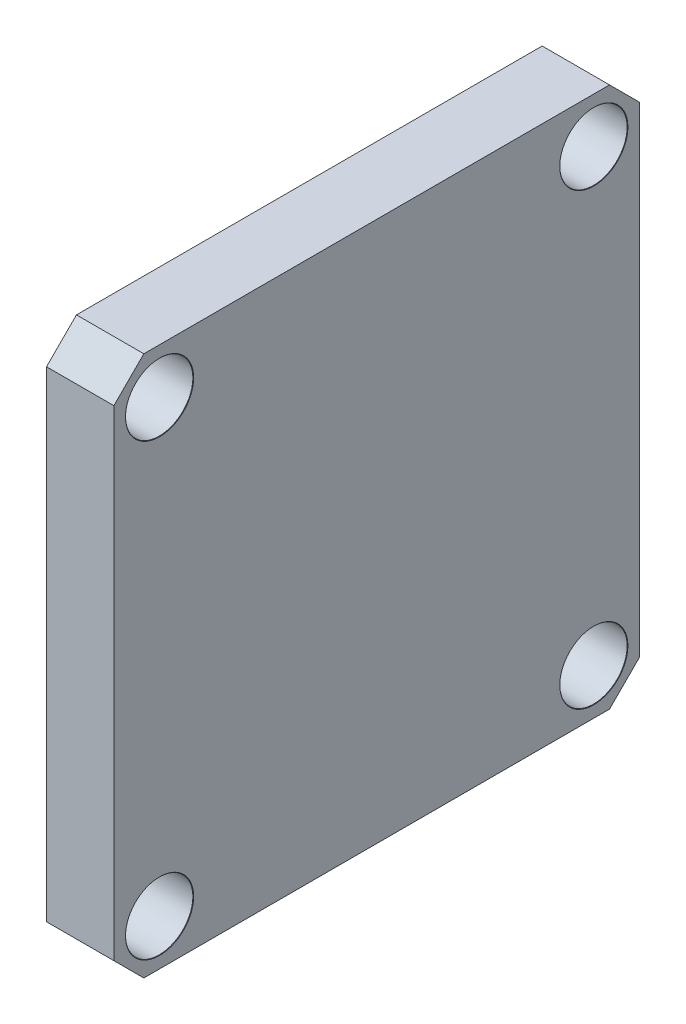
SolidWorks part; units mm, degrees
ref_plane "Спереди" through (0, 0, 0) normal (0, 0, 1) x (1, 0, 0)
ref_plane "Сверху" through (0, 0, 0) normal (0, 1, 0) x (1, 0, 0)
ref_plane "Справа" through (0, 0, 0) normal (1, 0, 0) x (0, 0, -1)
sketch "Эскиз1" plane through (0, 0, 0) normal (1, 0, 0) x (0, 0, -1)
  line L1 (-17.55, -18.05) -> (17.55, -18.05)
  line L2 (-17.55, -18.05) -> (-17.55, 18.05)
  line L3 (-17.55, 18.05) -> (17.55, 18.05)
  line L4 (17.55, -18.05) -> (17.55, 18.05)
  line L5 (-17.55, -18.05) -> (17.55, 18.05) construction
  line L6 (-17.55, 18.05) -> (17.55, -18.05) construction
  point P0 (0, 0)
  dimension "D1" = 36.1
  dimension "D2" = 35.1
extrude "Бобышка-Вытянуть1" add sketch "Эскиз1" along normal blind 4.5
chamfer "Фаска1" distance 2 angle 45 4 edges at (2.25, -18.05, -17.55) (2.25, 18.05, -17.55) (2.25, -18.05, 17.55) (2.25, 18.05, 17.55)
ref_axis "Ось1" through (-17.3885, 0, 0) along (1, 0, 0)
sketch "Эскиз2" plane through (4.5, 0, 0) normal (1, 0, 0) x (0, 0, -1)
  line L1 (-14.5, -15) -> (14.5, -15)
  line L2 (-14.5, -15) -> (-14.5, 15)
  line L3 (-14.5, 15) -> (14.5, 15)
  line L4 (14.5, -15) -> (14.5, 15)
  line L5 (-14.5, -15) -> (14.5, 15) construction
  line L6 (-14.5, 15) -> (14.5, -15) construction
  point P0 (0, 0)
  dimension "D1" = 29
  dimension "D2" = 30
hole_wizard "Отверстие с зазором M41" positions "Трехмерный эскиз1" profile "Эскиз4" hole size "M4" standard "ISO" end condition through all
sketch3d "Трехмерный эскиз1"
  point P0 (4.5, 15, -14.5)
  point P3 (4.5, 15, 14.5)
  point P6 (4.5, -15, 14.5)
  point P9 (4.5, -15, -14.5)
sketch "Эскиз4" plane through (4.5, 15, -14.5) normal (0, 1, 0) x (0, 0, -1)
  line L0 (0, 0) -> (0, 4.5)
  line L1 (0, 4.5) -> (2.25, 4.5)
  line L2 (2.25, 4.5) -> (2.25, 0.025)
  line L3 (2.25, 0.025) -> (2.275, 0)
  line L5 (2.275, 0) -> (0, 0)
  line L6 (-2.25, 0.025) -> (-2.275, 0) construction
  line L11 (0, -6.35) -> (0, 107.95) construction
  dimension "Диаметр сквозного отверстия" = 4.5
  dimension "Глубина сквозного отверстия" = 4.5
  dimension "Диаметр передней зенковки" = 4.55
  dimension "Угол передней зенковки" = 90
